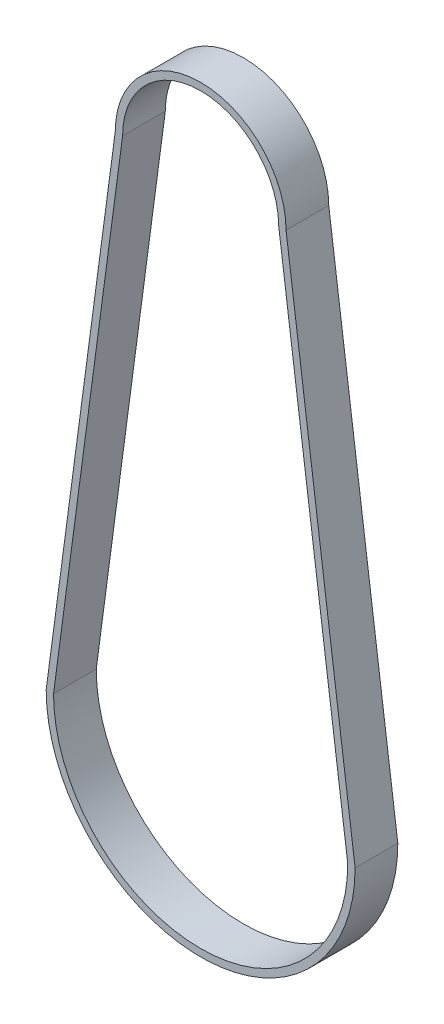
SolidWorks part; units mm, degrees
material "NEOPREN"
ref_plane "Ebene vorne" through (0, 0, 0) normal (0, 0, 1) x (1, 0, 0)
ref_plane "Ebene oben" through (0, 0, 0) normal (0, 1, 0) x (1, 0, 0)
ref_plane "Ebene rechts" through (0, 0, 0) normal (1, 0, 0) x (0, 0, -1)
sketch "Skizze2" plane through (0, 0, 0) normal (0, 0, 1) x (1, 0, 0)
  line L0 (0, 0) -> (1, 0) construction
  line L1 (0, 0) -> (0, 1) construction
  line L2 (47.3975, 6.3806) -> (87.4611, -291.2261)
  line L3 (-87.4611, -291.2261) -> (-47.3975, 6.3806)
  arc A0 (-47.3975, 6.3806) -> (47.3975, 6.3806) centre (0, 0) cw
  arc A1 (87.4611, -291.2261) -> (-87.4611, -291.2261) centre (0, -303) cw
sketch "Skizze3" plane through (0, 0, 0) normal (0, 0, 1) x (1, 0, 0)
  line L0 (-49.975, 0) -> (-90.4, -303)
  line L1 (49.975, 0) -> (90.4, -303)
  line L2 (86.1, -303) -> (45.675, 0)
  line L3 (-45.675, 0) -> (-86.1, -303)
  arc A0 (49.975, 0) -> (-49.975, 0) centre (0, 0) ccw
  arc A1 (45.675, 0) -> (-45.675, 0) centre (0, 0) ccw
  arc A2 (-90.4, -303) -> (90.4, -303) centre (0, -303) ccw
  arc A3 (-86.1, -303) -> (86.1, -303) centre (0, -303) ccw
  arc A4 (-87.4611, -291.2261) -> (87.4611, -291.2261) centre (0, -303) ccw construction
  arc A5 (47.3975, 6.3806) -> (-47.3975, 6.3806) centre (0, 0) ccw construction
  dimension "D1" = 2.15
  dimension "D2" = 2.15
  dimension "D3" = 2.15
  dimension "D4" = 2.15
extrude "Aufsatz-Linear austragen1" add sketch "Skizze3" along normal blind 12.5 and the other way blind 12.5
